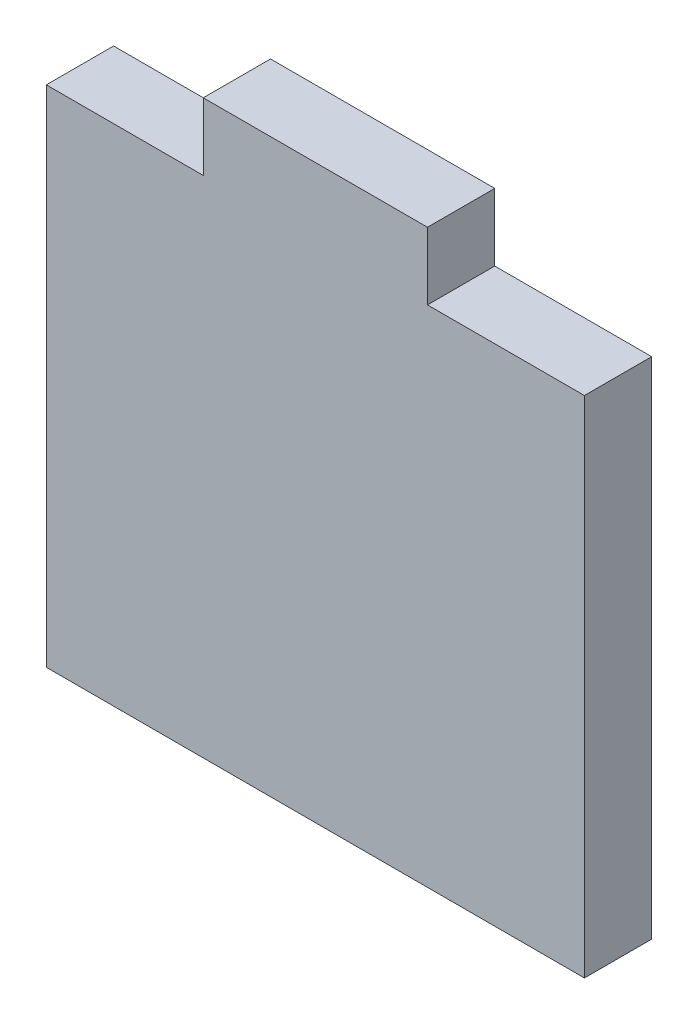
SolidWorks part; units mm, degrees
ref_plane "Plan de face" through (0, 0, 0) normal (0, 0, 1) x (1, 0, 0)
ref_plane "Plan de dessus" through (0, 0, 0) normal (0, 1, 0) x (1, 0, 0)
ref_plane "Plan de droite" through (0, 0, 0) normal (1, 0, 0) x (0, 0, -1)
sketch "Esquisse1" plane through (0, 0, 0) normal (0, 0, 1) x (1, 0, 0)
  line L1 (-53.4278, 35.3167) -> (-5.4278, 35.3167)
  line L2 (-53.4278, 35.3167) -> (-53.4278, -9.6833)
  line L3 (-53.4278, -9.6833) -> (-5.4278, -9.6833)
  line L4 (-5.4278, 35.3167) -> (-5.4278, -9.6833)
  dimension "D1" = 45
  dimension "D2" = 48
extrude "Boss.-Extru.1" add sketch "Esquisse1" along normal blind 6
sketch "Esquisse3" plane through (0, 0, 6) normal (0, 0, 1) x (1, 0, 0)
  line L0 (-5.4278, 35.3167) -> (-53.4278, 35.3167) construction
  line L1 (-39.4278, 35.3167) -> (-19.4278, 35.3167)
  line L2 (-39.4278, 35.3167) -> (-39.4278, 41.3167)
  line L3 (-39.4278, 41.3167) -> (-19.4278, 41.3167)
  line L4 (-19.4278, 35.3167) -> (-19.4278, 41.3167)
  line L5 (-5.4278, -9.6833) -> (-5.4278, 35.3167) construction
  dimension "D1" = 6
  dimension "D2" = 20
  dimension "D3" = 14
extrude "Boss.-Extru.2" add sketch "Esquisse3" against normal blind 6
